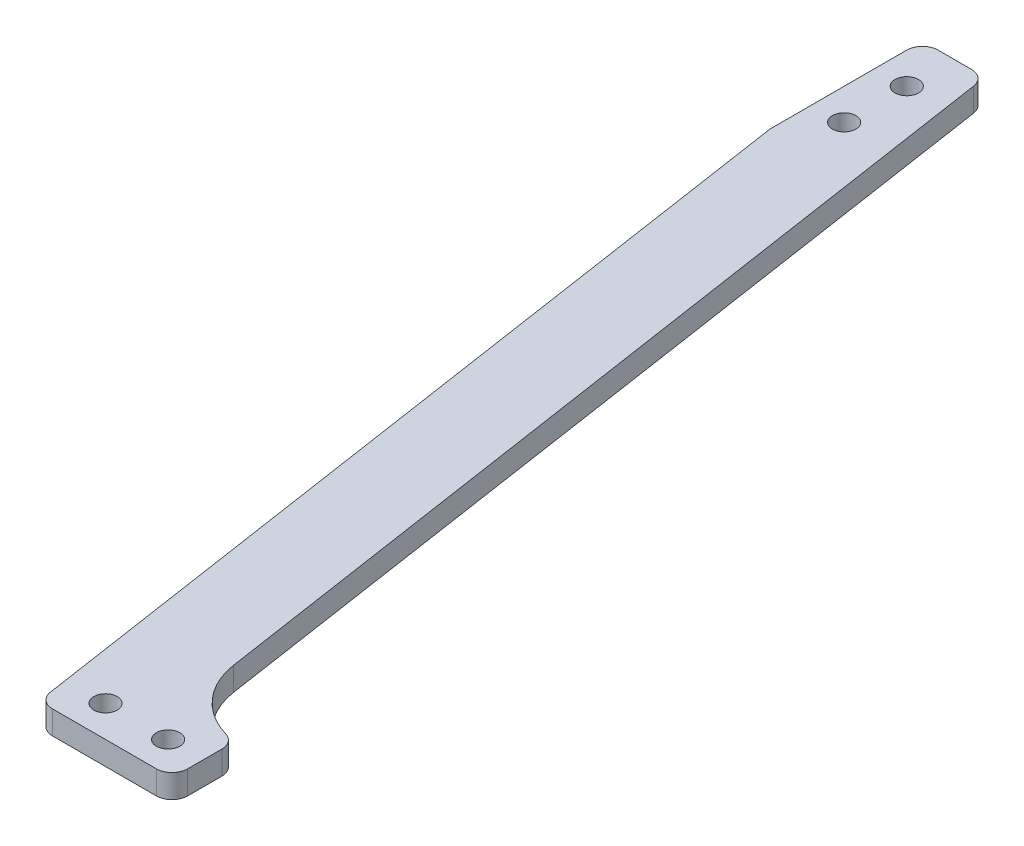
SolidWorks part; units mm, degrees
material "Thornel Mat VMA"
ref_plane "前视基准面" through (0, 0, 0) normal (0, 0, 1) x (1, 0, 0)
ref_plane "上视基准面" through (0, 0, 0) normal (0, 1, 0) x (1, 0, 0)
ref_plane "右视基准面" through (0, 0, 0) normal (1, 0, 0) x (0, 0, -1)
other "Configuration Table"
sketch "草图1" plane through (0, 0, 0) normal (0, 1, 0) x (1, 0, 0)
  line L0 (0, 0) -> (0, 154.6523) construction
  line L1 (0, 0) -> (198.8272, 0) construction
  line L2 (0, 110) -> (0, 129.5)
  line L3 (0, 129.5) -> (8, 129.5)
  line L5 (33.6, 8) -> (33.6, 0)
  line L6 (33.6, 0) -> (16.6, 0)
  line L7 (16.6, 0) -> (0, 110)
  line L8 (8, 129.5) -> (26.3355, 8)
  line L9 (26.3355, 8) -> (33.6, 8)
  circle A0 centre (21.1, 4) radius 1.5
  circle A1 centre (29.1, 4) radius 1.5
  circle A2 centre (4, 115.5) radius 1.5
  circle A3 centre (4, 123.5) radius 1.5
  dimension "D3" = 3
  dimension "D8" = 3
  dimension "D9" = 8
  dimension "D10" = 3
  dimension "D11" = 3
  dimension "D12" = 8
  dimension "D14" = 4
  dimension "D15" = 115.5
  dimension "D16" = 4
  dimension "D17" = 4
  dimension "D1" = 110
  dimension "D2" = 16.6
  dimension "D4" = 8
  dimension "D5" = 8
  dimension "D6" = 17
  dimension "D7" = 19.5
  dimension "D13" = 4
  dimension "D18" = 21.1
extrude "凸台-拉伸1" add sketch "草图1" along normal blind 3
fillet "圆角1" radius 10 1 edges at (26.3355, 1.5, -8)
fillet "圆角2" radius 2 4 edges at (8, 1.5, -129.5) (0, 1.5, -129.5) (16.6, 1.5, 0) (33.6, 1.5, 0)
fillet "圆角3" radius 2 1 edges at (33.6, 1.5, -8)
